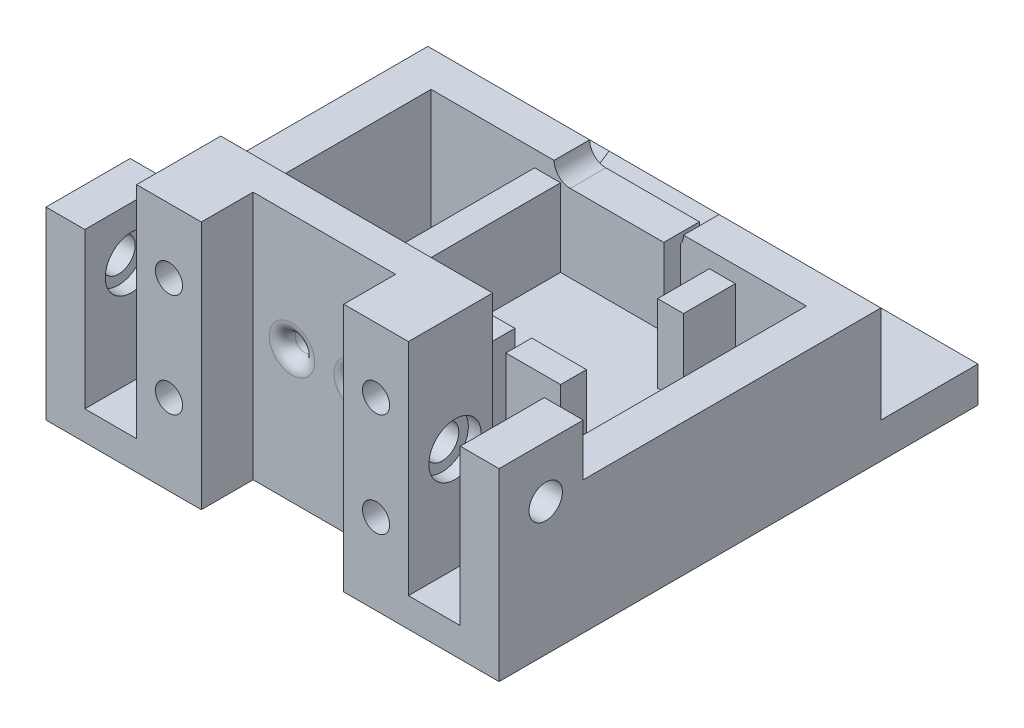
SolidWorks part; units mm, degrees
material "PBT General Purpose"
ref_plane "Front Plane" through (0, 0, 0) normal (0, 0, 1) x (1, 0, 0)
ref_plane "Top Plane" through (0, 0, 0) normal (0, 1, 0) x (1, 0, 0)
ref_plane "Right Plane" through (0, 0, 0) normal (1, 0, 0) x (0, 0, -1)
sketch "Sketch1" plane through (0, 0, 0) normal (0, 1, 0) x (1, 0, 0)
  line L0 (-29, 24) -> (-29, -29.5)
  line L1 (-35, 29.5) -> (35, 29.5)
  line L2 (-35, 29.5) -> (-35, -29.5)
  line L3 (-35, -29.5) -> (-29, -29.5)
  line L4 (35, 29.5) -> (35, -29.5)
  line L6 (29, 24) -> (29, -29.5)
  line L8 (-29, -23.5) -> (29, -23.5) construction
  line L9 (-29, 23.5) -> (-29, -23.5) construction
  line L10 (29, 23.5) -> (29, -23.5) construction
  line L11 (29, -29.5) -> (35, -29.5)
  line L12 (-35, -29.5) -> (35, -29.5) construction
  line L13 (-29, 23.5) -> (29, 23.5) construction
  line L14 (-29, 24) -> (29, 24)
  point P4 (0, 29.5)
  point P5 (35, 0)
  dimension "D1" = 70
  dimension "D2" = 59
  dimension "D4" = 5.5
  dimension "D3" = 6
extrude "Boss-Extrude1" add sketch "Sketch1" against normal blind 20.5
sketch "Sketch5" plane through (0, -20.5, 0) normal (0, 1, 0) x (1, 0, 0)
  line L0 (-29, 24) -> (29, 24) construction
  line L1 (-9, 24) -> (14, 24)
  line L2 (-9, 24) -> (-9, 1)
  line L3 (-9, 1) -> (14, 1)
  line L4 (14, 24) -> (14, 1)
  line L6 (29, -29.5) -> (29, 24) construction
  dimension "D1" = 23
  dimension "D2" = 23
  dimension "D4" = 15
extrude "Boss-Extrude3" add sketch "Sketch5" along normal offset from surface (6 mm away) 14.5 separate body up to face at (0, 0, 1.375)
sketch "Sketch16" plane through (0, -20.5, 0) normal (0, -1, 0) x (1, 0, 0)
  line L1 (18, -24) -> (14, -24)
  line L2 (18, -24) -> (18, 3)
  line L3 (18, 3) -> (-13, 3)
  line L4 (-9, -24) -> (14, -24)
  line L5 (-9, -1) -> (-9, -24)
  line L6 (14, -1) -> (-9, -1)
  line L7 (14, -24) -> (14, -1)
  line L9 (-9, -1) -> (-9, -24)
  line L10 (14, -1) -> (-9, -1)
  line L11 (14, -24) -> (14, -1)
  line L12 (-13, -24) -> (-13, 3)
  line L13 (-9, -24) -> (-13, -24)
  line L14 (-29, -24) -> (29, -24) construction
  dimension "D2" = 4
  dimension "D3" = 4
  dimension "D4" = 4
  dimension "D1" = 0
extrude "Boss-Extrude6" add sketch "Sketch16" against normal offset from surface (18 mm away) 12 up to face at (2.5, -14.5, -12.5) offset beyond the face yes
sketch "Sketch18" plane through (0, 0, 0) normal (0, 1, 0) x (1, 0, 0)
  line L6 (18, -3) -> (-13, -3) construction
  line L7 (6.95, -3) -> (9.55, -3)
  line L8 (6.95, -3) -> (6.95, 1)
  line L9 (6.95, 1) -> (9.55, 1)
  line L10 (9.55, -3) -> (9.55, 1)
  line L11 (-9, 1) -> (14, 1) construction
  line L12 (14, 1) -> (-9, 1) construction
  line L13 (-4.55, -3) -> (-2.55, -3)
  line L14 (-4.55, -3) -> (-4.55, 1)
  line L15 (-4.55, 1) -> (-2.55, 1)
  line L16 (-2.55, -3) -> (-2.55, 1)
  line L17 (18, 24) -> (18, -3) construction
  line L18 (14, 1) -> (18, 1)
  line L19 (14, 1) -> (14, 16)
  line L20 (14, 16) -> (18, 16)
  line L21 (18, 1) -> (18, 16)
  line L28 (9.55, 24) -> (9.55, 29.5)
  line L29 (9.55, 29.5) -> (6.95, 29.5)
  line L30 (6.95, 24) -> (6.95, 29.5)
  line L31 (35, 29.5) -> (-35, 29.5) construction
  line L32 (6.95, 24) -> (9.55, 24)
  line L33 (-29, 24) -> (29, 24) construction
  dimension "D1" = 15
  dimension "D2" = 4.45
  dimension "D3" = 2.6
  dimension "D4" = 9.5
  dimension "D5" = 2
extrude "Cut-Extrude10" cut sketch "Sketch18" against normal up to surface (14.5 mm away) up to face at (2.5, -14.5, -12.5)
sketch "gear_alignment_sketch" plane through (35, 0, 0) normal (1, 0, 0) x (0, 0, -1)
  line L0 (7, 0) -> (7, -20.5) construction
  line L1 (-29.5, 0) -> (29.5, 0) construction
  line L2 (-29.5, -20.5) -> (29.5, -20.5) construction
  line L3 (-992.2945, 0) -> (49007.7055, 0) construction
  line L5 (-29.5, 0) -> (29.5, 0) construction
  line L7 (-22.2916, 0) -> (7, -8.5) construction
  line L8 (16, -14.5) -> (24, -14.5) construction
  point P7 (-22.2916, 0)
  point P10 (7, -8.5)
  dimension "D1" = 6
  dimension "D3" = 30.5
  dimension "D2" = 6
sketch "Sketch8" plane through (0, 0, 0) normal (0, 1, 0) x (1, 0, 0)
  line L1 (35, -16.5) -> (29, -16.5)
  line L2 (35, -16.5) -> (35, -29.5)
  line L3 (35, -29.5) -> (29, -29.5)
  line L4 (29, -16.5) -> (29, -29.5)
  line L9 (29, 24) -> (29, -29.5) construction
  line L10 (35, -29.5) -> (35, 29.5) construction
  dimension "D1" = 13
extrude "Boss-Extrude4" add sketch "Sketch8" along normal blind 8
sketch "Sketch7" plane through (35, 0, 0) normal (1, 0, 0) x (0, 0, -1)
  circle A0 centre (-22.2916, 0) radius 2.575
  dimension "D1" = 5.15
extrude "x" cut sketch "Sketch7" against normal up to next
sketch "Sketch9" plane through (29, 0, 0) normal (1, 0, 0) x (0, 0, -1)
  circle A0 centre (-22.2916, 0) radius 4.05
  dimension "D1" = 8.1
extrude "Cut-Extrude4" cut sketch "Sketch9" along normal blind 2
sketch "Sketch10" plane through (0, -20.5, 0) normal (0, -1, 0) x (1, 0, 0)
  line L1 (0, 16.5) -> (29, 16.5)
  line L3 (0, 29.5) -> (29, 29.5)
  line L4 (29, 16.5) -> (29, 29.5)
  line L5 (29, 29.5) -> (29, -24) construction
  line L6 (35, 16.5) -> (29, 16.5) construction
  line L7 (29, 29.5) -> (35, 29.5) construction
  line L8 (0, -1000) -> (0, 49000) construction
  line L9 (0, 16.5) -> (0, 29.5)
extrude "Boss-Extrude5" add sketch "Sketch10" against normal up to surface (28.5 mm away) up to face at (32, 8, 23)
sketch "Sketch12" plane through (0, 8, 0) normal (0, 1, 0) x (1, 0, 0)
  line L0 (0, -29.5) -> (35, -29.5) construction
  line L1 (29, -16.5) -> (21, -16.5)
  line L2 (29, -16.5) -> (29, -29.5)
  line L3 (29, -29.5) -> (21, -29.5)
  line L4 (21, -16.5) -> (21, -29.5)
  dimension "D1" = 8
extrude "Cut-Extrude6" cut sketch "Sketch12" against normal blind 24
sketch "Sketch13" plane through (21, 0, 0) normal (1, 0, 0) x (0, 0, -1)
  circle A0 centre (-22.2916, 0) radius 2.575
  circle A1 centre (-22.2916, 0) radius 2.575 construction
extrude "Cut-Extrude7" cut sketch "Sketch13" against normal blind 6
sketch "Sketch14" plane through (21, 0, 0) normal (1, 0, 0) x (0, 0, -1)
  circle A0 centre (-22.2916, 0) radius 4.05
  circle A1 centre (-22.2916, 0) radius 4.05 construction
extrude "Cut-Extrude8" cut sketch "Sketch14" against normal blind 2
mirror "Mirror1" about plane through (0, 0, 0) normal (1, 0, 0) of "Cut-Extrude8", "Cut-Extrude7", "Cut-Extrude6", "Boss-Extrude5", "Boss-Extrude4", "x", "Cut-Extrude4"
sketch "Sketch35" plane through (0, 0, 29.5) normal (0, 0, 1) x (1, 0, 0)
  line L0 (-5, 0) -> (5, 0) construction
  line L1 (-21, 8) -> (21, 8) construction
  circle A2 centre (-5, 0) radius 1.5
  circle A3 centre (5, 0) radius 1.5
  point P3 (0, 0)
  point P16 (0, 8)
  dimension "D1" = 3
  dimension "D2" = 3
  dimension "D3" = 10
extrude "Cut-Extrude21" cut sketch "Sketch35" against normal up to next
sketch "Sketch36" plane through (0, 8, 0) normal (0, 1, 0) x (1, 0, 0)
  line L0 (5, -29.5) -> (5, -16.5) construction
  line L1 (-21, -29.5) -> (21, -29.5) construction
  line L2 (21, -16.5) -> (-21, -16.5) construction
  line L3 (0, -29.5) -> (0, -16.5) construction
  line L4 (3.5, -29.5) -> (6.5, -29.5) construction
  line L5 (-5, -29.5) -> (5, -29.5)
  line L6 (5, -29.5) -> (11, -29.5)
  line L7 (11, -21.5) -> (11, -29.5)
  line L8 (21, -16.5) -> (21, -29.5) construction
  line L9 (11, -21.5) -> (-11, -21.5)
  line L10 (-11, -21.5) -> (-11, -29.5)
  line L11 (-5, -29.5) -> (-11, -29.5)
  point P18 (0, -21.5)
  dimension "D1" = 10
  dimension "D2" = 5
extrude "Cut-Extrude22" cut sketch "Sketch36" against normal up to next
fillet "Fillet1" radius 2 4 edges at (6.5, 0, 16.5) (-3.5, 0, 16.5) (3.5, 0, 21.5) (-6.5, 0, 21.5)
sketch "Sketch37" plane through (0, 8, 0) normal (0, 1, 0) x (1, 0, 0)
  line L8 (-11, -21.5) -> (11, -21.5)
  line L9 (11, -21.5) -> (11, -29.5)
  line L10 (11, -29.5) -> (21, -29.5)
  line L11 (21, -29.5) -> (21, -16.5)
  line L12 (21, -16.5) -> (-21, -16.5)
  line L13 (-21, -16.5) -> (-21, -29.5)
  line L14 (-21, -29.5) -> (-11, -29.5)
  line L15 (-11, -29.5) -> (-11, -21.5)
  line L16 (-11, -21.5) -> (11, -21.5)
  line L17 (11, -21.5) -> (11, -29.5)
  line L18 (11, -29.5) -> (21, -29.5)
  line L19 (21, -29.5) -> (21, -16.5)
  line L20 (21, -16.5) -> (-21, -16.5)
  line L21 (-21, -16.5) -> (-21, -29.5)
  line L22 (-21, -29.5) -> (-11, -29.5)
  line L23 (-11, -29.5) -> (-11, -21.5)
  dimension "D1" = 0
extrude "Boss-Extrude7" add sketch "Sketch37" along normal blind 10
sketch "Sketch34" plane through (0, 0, 29.5) normal (0, 0, 1) x (1, 0, 0)
  line L2 (0, -20.5) -> (0, 8) construction
  line L8 (11, 8) -> (21, 8) construction
  line L9 (11, -20.5) -> (35, -20.5) construction
  circle A0 centre (16, -8) radius 2.1
  circle A4 centre (16, 8) radius 2.1
  circle A5 centre (-16, 8) radius 2.1
  circle A6 centre (-16, -8) radius 2.1
  point P8 (0, -20.5)
  dimension "D1" = 8
  dimension "D2" = 4.2
  dimension "D4" = 4.2
  dimension "D3" = 16
  dimension "D5" = 16
extrude "Cut-Extrude20" cut sketch "Sketch34" against normal blind 10
sketch "Sketch38" plane through (0, 0, -29.5) normal (0, 0, -1) x (-1, 0, 0)
  line L1 (-35, -20.5) -> (35, -20.5)
  line L2 (-35, -20.5) -> (-35, -15)
  line L3 (-35, -15) -> (35, -15)
  line L4 (35, -20.5) -> (35, -15)
  line L5 (35, -20.5) -> (35, 0) construction
  line L6 (-6.95, 0) -> (35, 0) construction
  dimension "D1" = 15
extrude "Boss-Extrude8" add sketch "Sketch38" along normal blind 15
sketch "Sketch39" plane through (0, -15, 0) normal (0, 1, 0) x (1, 0, 0)
  line L0 (35, 37) -> (-35, 37) construction
  line L1 (35, 44.5) -> (35, 29.5) construction
  line L2 (-35, 44.5) -> (-35, 29.5) construction
  line L3 (0, 29.5) -> (0, 37) construction
  line L4 (-35, 29.5) -> (35, 29.5) construction
  line L5 (-35, 44.5) -> (35, 44.5) construction
  line L6 (11.5, 29.5) -> (14.5, 37)
  line L14 (14.5, 37) -> (-14.5, 37)
  line L15 (11.5, 29.5) -> (-11.5, 29.5)
  line L16 (-11.5, 29.5) -> (-14.5, 37)
  dimension "D1" = 23
  dimension "D2" = 3
  dimension "D3" = 7.5
extrude "Boss-Extrude9" add sketch "Sketch39" along normal blind 7.5
sketch "Sketch40" plane through (0, 0, -29.5) normal (0, 0, -1) x (-1, 0, 0)
  line L0 (-6.95, 0) -> (35, 0) construction
  line L1 (-7.5, 0) -> (7.5, 0) construction
  line L2 (-7.5, 2.5) -> (7.5, 2.5)
  line L3 (-7.5, -2.5) -> (7.5, -2.5)
  arc A0 (-7.5, 2.5) -> (-7.5, -2.5) centre (-7.5, 0) ccw
  arc A1 (7.5, -2.5) -> (7.5, 2.5) centre (7.5, 0) ccw
  point P4 (0, 0)
  dimension "D1" = 2.5
  dimension "D2" = 15
extrude "Cut-Extrude23" cut sketch "Sketch40" against normal up to next (5.5 mm away)
equation "\"bushing_hole_outer_diameter\"= 8.1mm"
equation "\"bushing_hole_inner_diameter\"= 5.15mm"
equation "\"bushing_flange_depth\"= 2mm"
equation "\"D1@Boss-Extrude3\"=12 + 2.5"
equation "\"gear_spacing\"= 30.5mm"
equation "\"D3@gear_alignment_sketch\" = \"gear_spacing\""
equation "\"D1@Sketch7\"=\"bushing_hole_inner_diameter\""
equation "\"D1@Sketch9\"=\"bushing_hole_outer_diameter\""
equation "\"D1@Cut-Extrude4\"=\"bushing_flange_depth\""
equation "\"D1@Cut-Extrude8\"=\"bushing_flange_depth\""
equation "\"body_height\"= 41mm"
equation "\"D1@Boss-Extrude1\"= \"body_height\" / 2"
